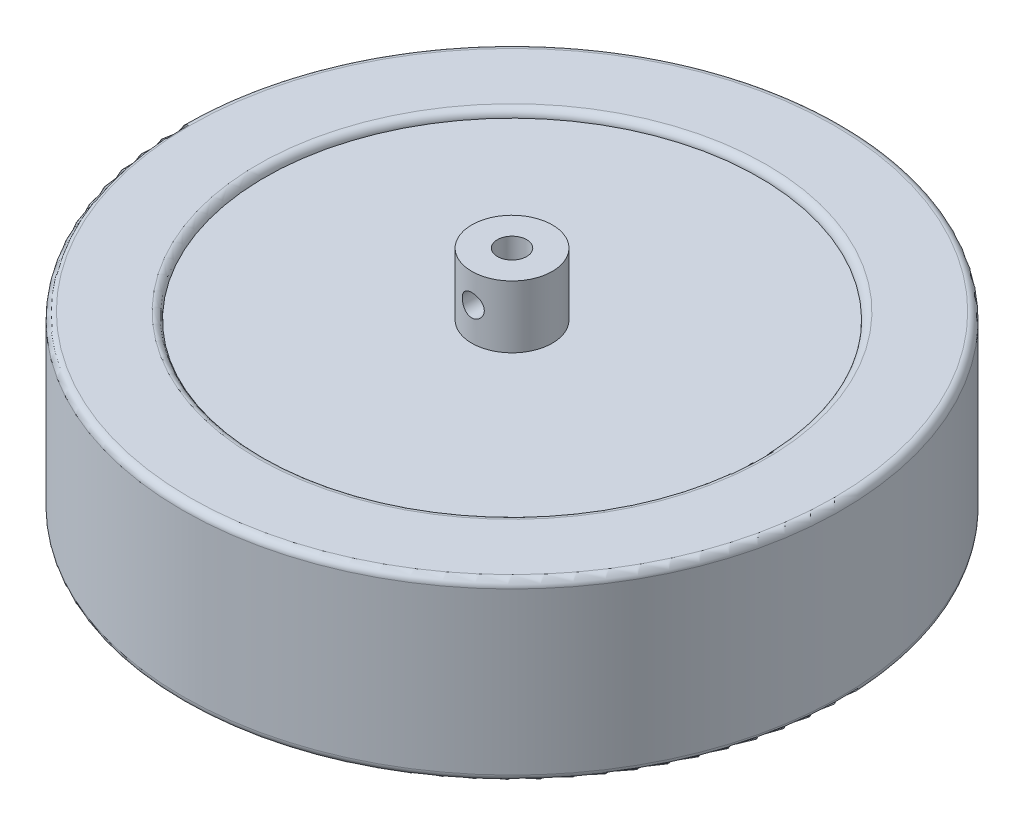
SolidWorks part; units mm, degrees
ref_plane "前视基准面" through (0, 0, 0) normal (0, 0, 1) x (1, 0, 0)
ref_plane "上视基准面" through (0, 0, 0) normal (0, 1, 0) x (1, 0, 0)
ref_plane "右视基准面" through (0, 0, 0) normal (1, 0, 0) x (0, 0, -1)
sketch "Sketch2" plane through (0, 0, 0) normal (0, 1, 0) x (1, 0, 0)
  circle A0 centre (0, 0) radius 90
  dimension "D1" = 180
extrude "Boss-Extrude1" add sketch "Sketch2" along normal blind 48
sketch "Sketch3" plane through (0, 48, 0) normal (0, 1, 0) x (1, 0, 0)
  circle A0 centre (0, 0) radius 67.5
  dimension "D1" = 135
extrude "Cut-Extrude1" cut sketch "Sketch3" against normal blind 2
sketch "Sketch4" plane through (0, 0, 0) normal (0, -1, 0) x (1, 0, 0)
  circle A0 centre (0, 0) radius 67.5
  dimension "D1" = 135
extrude "Cut-Extrude2" cut sketch "Sketch4" against normal blind 2
fillet "Fillet1" radius 2 4 edges at (0, 0, -67.5) (0, 48, 67.5) (0, 0, 90) (0, 48, 90)
sketch "草图1" plane through (0, 46, 0) normal (0, 1, 0) x (1, 0, 0)
  circle A0 centre (0, 0) radius 11
  dimension "D1" = 22
extrude "凸台-拉伸1" add sketch "草图1" along normal blind 17
sketch "草图2" plane through (0, 63, 0) normal (0, 1, 0) x (1, 0, 0)
  circle A0 centre (0, 0) radius 4
  dimension "D1" = 8
extrude "切除-拉伸1" cut sketch "草图2" against normal blind 15
sketch "草图3" plane through (0, 0, 0) normal (0, 0, 1) x (1, 0, 0)
  line L0 (0, 64.2086) -> (0, 0) construction
  line L1 (-69.5, 0) -> (69.5, 0) construction
  line L2 (11, 63) -> (-11, 63) construction
  circle A0 centre (0, 55) radius 3
  dimension "D1" = 6
  dimension "D2" = 8
extrude "切除-拉伸2" cut sketch "草图3" along normal blind 15
